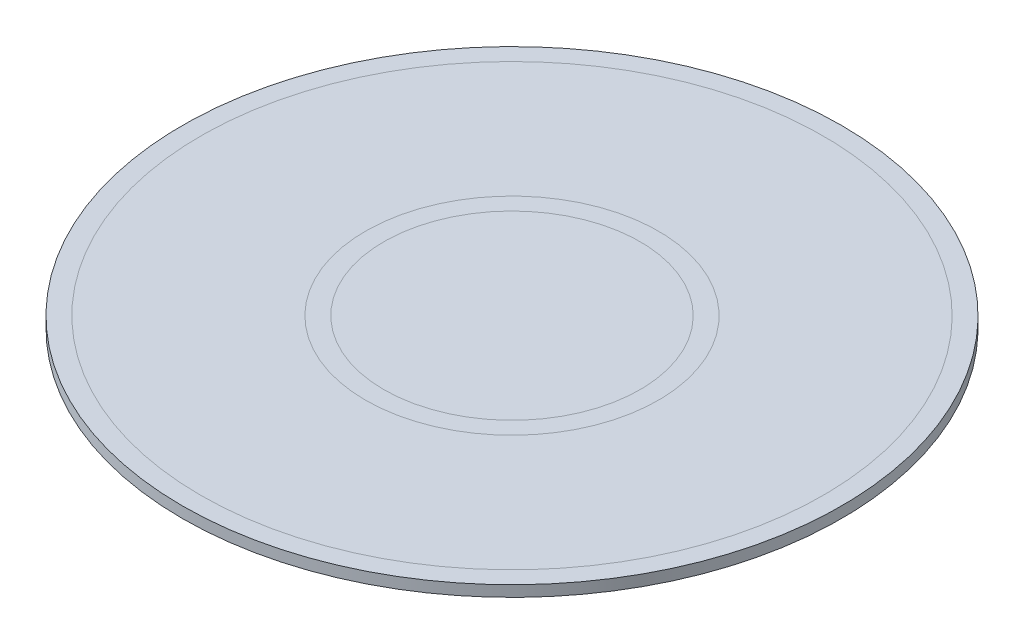
SolidWorks part; units mm, degrees
ref_plane "Front Plane" through (0, 0, 0) normal (0, 0, 1) x (1, 0, 0)
ref_plane "Top Plane" through (0, 0, 0) normal (0, 1, 0) x (1, 0, 0)
ref_plane "Right Plane" through (0, 0, 0) normal (1, 0, 0) x (0, 0, -1)
sketch "Sketch1" plane through (0, 0, 0) normal (0, 1, 0) x (1, 0, 0)
  circle A0 centre (0, 0) radius 9
  dimension "D1" = 18
extrude "Boss-Extrude1" add sketch "Sketch1" along normal blind 0.3
sketch "Sketch2" plane through (0, 0.3, 0) normal (0, 1, 0) x (1, 0, 0)
  circle A0 centre (0, 0) radius 9 construction
  circle A1 centre (0, 0) radius 9
  circle A2 centre (0, 0) radius 8.5
  dimension "D1" = 0.5
wrap "Wrap1" sketch "Sketch2" wrap type scribe source sketch "Sketch2" face at (0, 0.3, 9)
sketch "Sketch5" plane through (0, 0.3, 0) normal (0, 1, 0) x (1, 0, 0)
  circle A0 centre (0, 0) radius 4
  circle A1 centre (0, 0) radius 3.5
  dimension "D1" = 8
  dimension "D2" = 0.5
wrap "Wrap2" sketch "Sketch5" wrap type scribe source sketch "Sketch5" face at (0, 0.3, 8.5)
sketch "Sketch6" plane through (0, 0, 0) normal (0, -1, 0) x (1, 0, 0)
  circle A1 centre (0, 0) radius 8.5
  circle A2 centre (0, 0) radius 8.5
  circle A3 centre (0, 0) radius 9
  circle A4 centre (0, 0) radius 9
  dimension "D1" = 0
  dimension "D2" = 0
wrap "Wrap3" sketch "Sketch6" wrap type scribe source sketch "Sketch6"
sketch "Sketch7" plane through (0, 0, 0) normal (0, -1, 0) x (1, 0, 0)
  circle A1 centre (0, 0) radius 3.5
  circle A2 centre (0, 0) radius 3.5
  circle A3 centre (0, 0) radius 4
  circle A4 centre (0, 0) radius 4
  dimension "D1" = 0
  dimension "D2" = 0
wrap "Wrap4" sketch "Sketch7" wrap type scribe source sketch "Sketch7"
